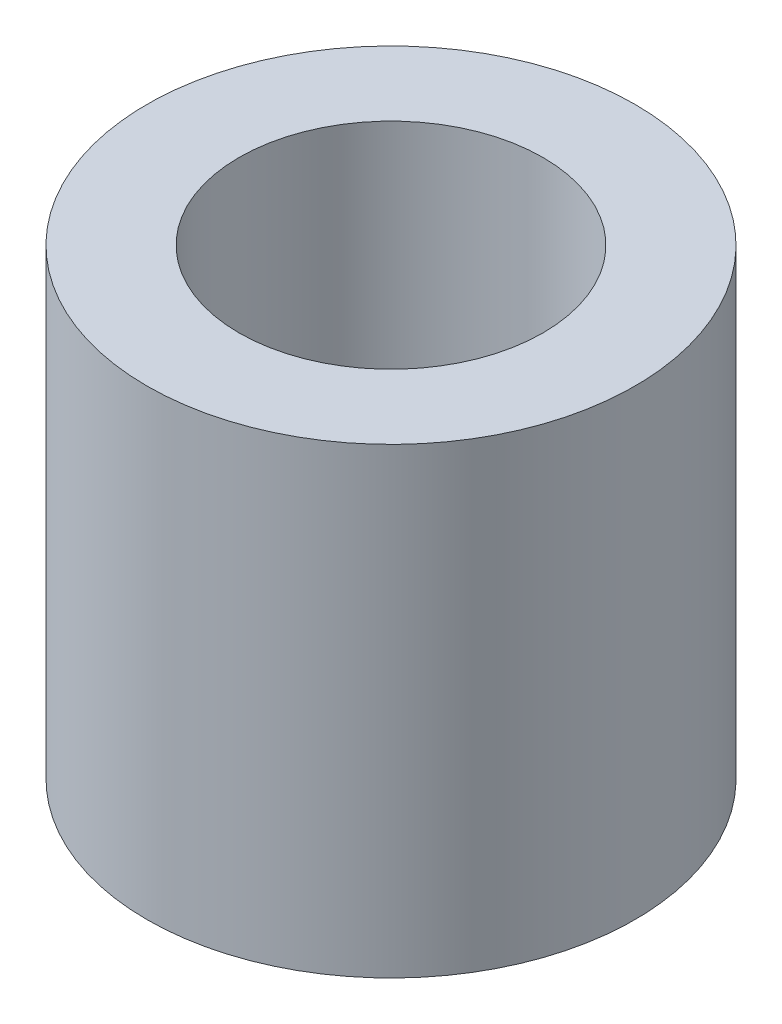
SolidWorks part; units mm, degrees
ref_plane "Front Plane" through (0, 0, 0) normal (0, 0, 1) x (1, 0, 0)
ref_plane "Top Plane" through (0, 0, 0) normal (0, 1, 0) x (1, 0, 0)
ref_plane "Right Plane" through (0, 0, 0) normal (1, 0, 0) x (0, 0, -1)
sketch "Sketch1" plane through (0, 0, 0) normal (0, 1, 0) x (1, 0, 0)
  circle A0 centre (0, 0) radius 10
  dimension "SLEEVE_OD" = 20
extrude "Boss-Extrude1" add sketch "Sketch1" along normal blind 18.9409
sketch "Sketch2" plane through (0, 0, 0) normal (0, 1, 0) x (1, 0, 0)
  circle A0 centre (0, 0) radius 6.2289
  dimension "BORE_D" = 12.4578
extrude "Cut-Extrude1" cut sketch "Sketch2" along normal through all
chamfer "Chamfer1" distance 1.3598 angle 69.02 rebuild error yes
